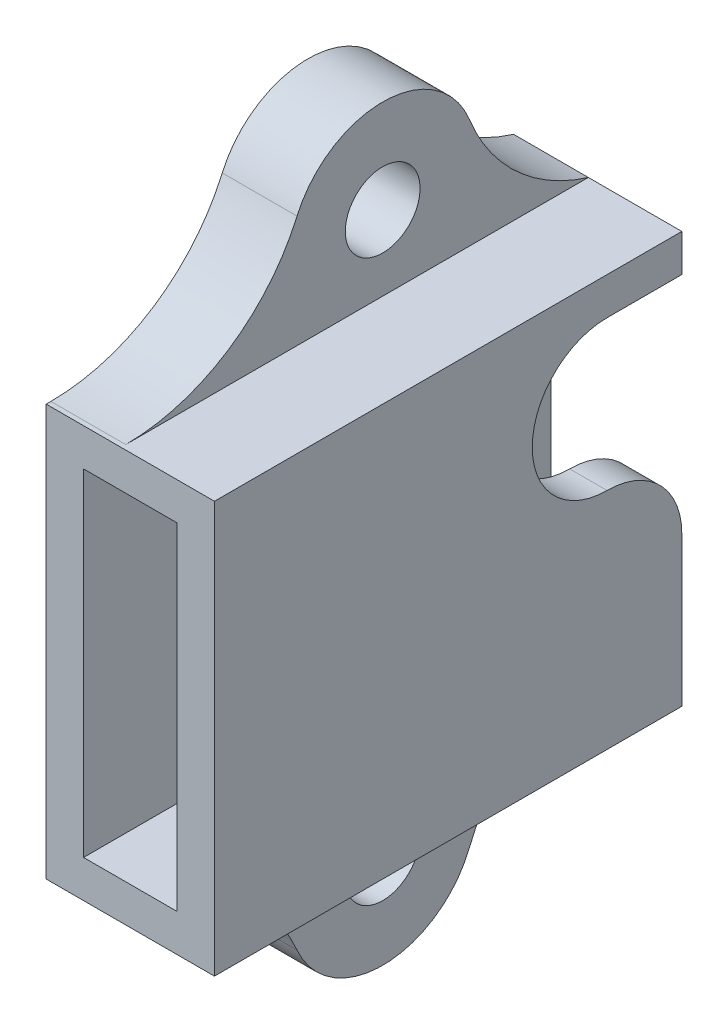
SolidWorks part; units mm, degrees
ref_plane "Plan de face" through (0, 0, 0) normal (0, 0, 1) x (1, 0, 0)
ref_plane "Plan de dessus" through (0, 0, 0) normal (0, 1, 0) x (1, 0, 0)
ref_plane "Plan de droite" through (0, 0, 0) normal (1, 0, 0) x (0, 0, -1)
sketch "Esquisse1" plane through (0, 0, 0) normal (0, 0, 1) x (1, 0, 0)
  line L1 (0, 0) -> (5, 0)
  line L2 (0, 0) -> (0, 18)
  line L3 (0, 18) -> (5, 18)
  line L4 (5, 0) -> (5, 18)
  line L5 (-2, -2) -> (7, -2)
  line L6 (-2, -2) -> (-2, 20)
  line L7 (-2, 20) -> (7, 20)
  line L8 (7, -2) -> (7, 20)
  point P9 (2.5, 20)
  dimension "D1" = 5
  dimension "D2" = 18
  dimension "D3" = 2
  dimension "D4" = 2
  dimension "D5" = 2
  dimension "D6" = 2
extrude "Boss.-Extru.1" add sketch "Esquisse1" along normal blind 25
sketch "Esquisse2" plane through (-2, 0, 0) normal (-1, 0, 0) x (0, 0, 1)
  line L2 (6, -2) -> (6, -6)
  line L3 (6, -6) -> (16, -6) construction
  line L4 (16, -6) -> (16, -2)
  line L5 (25, -2) -> (0, -2) construction
  line L6 (6, 20) -> (6, 24)
  line L7 (6, 24) -> (16, 24) construction
  line L8 (16, 24) -> (16, 20)
  line L9 (25, 20) -> (0, 20) construction
  line L10 (6, 20) -> (16, 20)
  line L11 (16, -2) -> (6, -2)
  line L12 (0, 20) -> (0, -2) construction
  arc A0 (6, 24) -> (16, 24) centre (11, 24) cw
  arc A1 (6, -6) -> (16, -6) centre (11, -6) ccw
  circle A2 centre (11, -6) radius 2
  circle A3 centre (11, 24) radius 2
  point P14 (11, -6)
  point P20 (11, 24)
  point P27 (6, -4)
  dimension "D4" = 4
  dimension "D1" = 4
  dimension "D2" = 4
  dimension "D3" = 30
  dimension "D5" = 6
  dimension "D6" = 10
extrude "Boss.-Extru.2" add sketch "Esquisse2" against normal blind 4
fillet "Congé1" radius 10 4 edges at (0, -2, 16) (0, 20, 16) (0, -2, 6) (0, 20, 6)
sketch "Esquisse3" plane through (0, 0, 0) normal (1, 0, 0) x (0, 0, -1)
  line L1 (0, 18) -> (-8, 18)
  line L2 (0, 18) -> (0, 10)
  line L3 (0, 10) -> (-8, 10)
  line L4 (-8, 18) -> (-8, 10)
  dimension "D1" = 8
  dimension "D2" = 8
extrude "Enlèv. mat.-Extru.1" cut sketch "Esquisse3" along normal through all
fillet "Congé2" radius 4 3 edges at (6, 10, 0) (6, 10, 8) (6, 18, 8)
